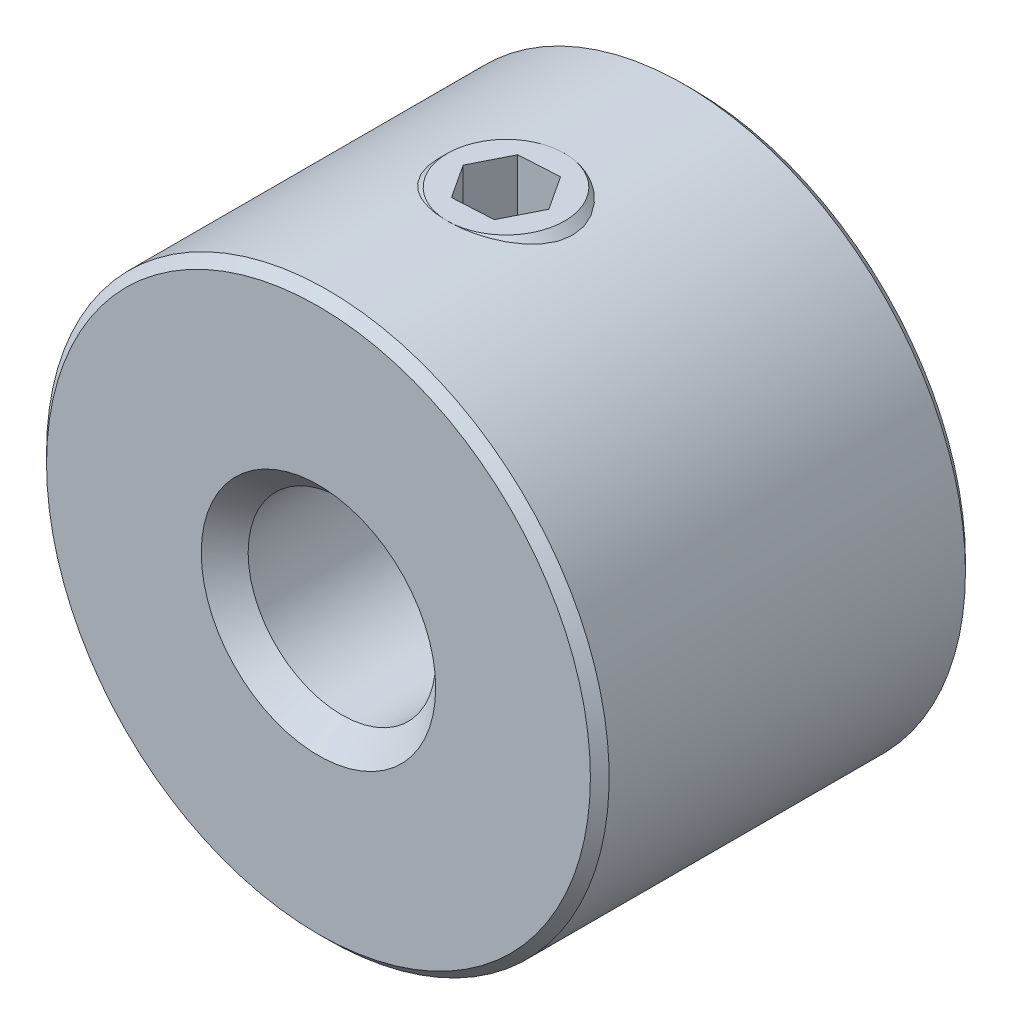
SolidWorks part; units mm, degrees
material "1060 Alloy"
material "Plain Carbon Steel"
material "1060 Alloy"
ref_plane "Front Plane" through (0, 0, 0) normal (0, 0, 1) x (1, 0, 0)
ref_plane "Top Plane" through (0, 0, 0) normal (0, 1, 0) x (1, 0, 0)
ref_plane "Right Plane" through (0, 0, 0) normal (1, 0, 0) x (0, 0, -1)
ref_axis "Axis1" through (0, 0, -7.6563) along (0, 0, 1)
sketch "Sketch1" plane through (0, 0, 0) normal (0, 1, 0) x (1, 0, 0)
  line L0 (2, 0) -> (2, -8)
  line L1 (2, -8) -> (6, -8)
  line L2 (6, -8) -> (6, 0)
  line L5 (6, 0) -> (2, 0)
  line L7 (0, 122.4579) -> (0, -141.6286) construction
  line L8 (0, 7.6563) -> (0, -14.3089) construction
  dimension "D1" = 4
  dimension "D2" = 12
  dimension "D5" = 8
revolve "Revolve1" add sketch "Sketch1" angle 360 about L7
sketch "Sketch2" plane through (0, 0, 0) normal (0, 1, 0) x (1, 0, 0)
  line L0 (-6, -8) -> (6, -8) construction
  line L1 (0, 3.6487) -> (0, -20.516) construction
  circle A0 centre (0, -4) radius 1.25
  dimension "D1" = 2.5
  dimension "D2" = 4
extrude "Cut-Extrude1" cut sketch "Sketch2" along normal through all
chamfer "Chamfer1" distance 0.2 angle 45 2 edges at (-6, 0, 8) (-6, 0, 0)
ref_plane "Plane1" through (0, 1.5, 0) normal (0, 1, 0) x (1, 0, 0)
sketch "Sketch4" plane through (0, 1.5, 0) normal (0, 1, 0) x (1, 0, 0)
  circle A0 centre (0, -4) radius 1.5
  dimension "D1" = 3
extrude "Boss-Extrude1" add sketch "Sketch4" along normal blind 4.5 separate body
chamfer "Chamfer2" distance 0.25 angle 45 1 edges at (0, 6, 5.5)
sketch "Sketch5" plane through (0, 6, 0) normal (0, 1, 0) x (1, 0, 0)
  line L1 (0.4746, -4.7244) -> (0.8647, -3.9512)
  line L2 (0.8647, -3.9512) -> (0.3901, -3.2268)
  line L3 (0.3901, -3.2268) -> (-0.4746, -3.2756)
  line L4 (-0.4746, -3.2756) -> (-0.8647, -4.0488)
  line L5 (-0.8647, -4.0488) -> (-0.3901, -4.7732)
  line L6 (-0.3901, -4.7732) -> (0.4746, -4.7244)
  circle A0 centre (0, -4) radius 0.75 construction
  dimension "D1" = 1.5
extrude "Cut-Extrude3" cut sketch "Sketch5" against normal blind 2
chamfer "Chamfer3" distance 0.5 angle 45 2 edges at (-2, 0, 0) (-2, 0, 8)
